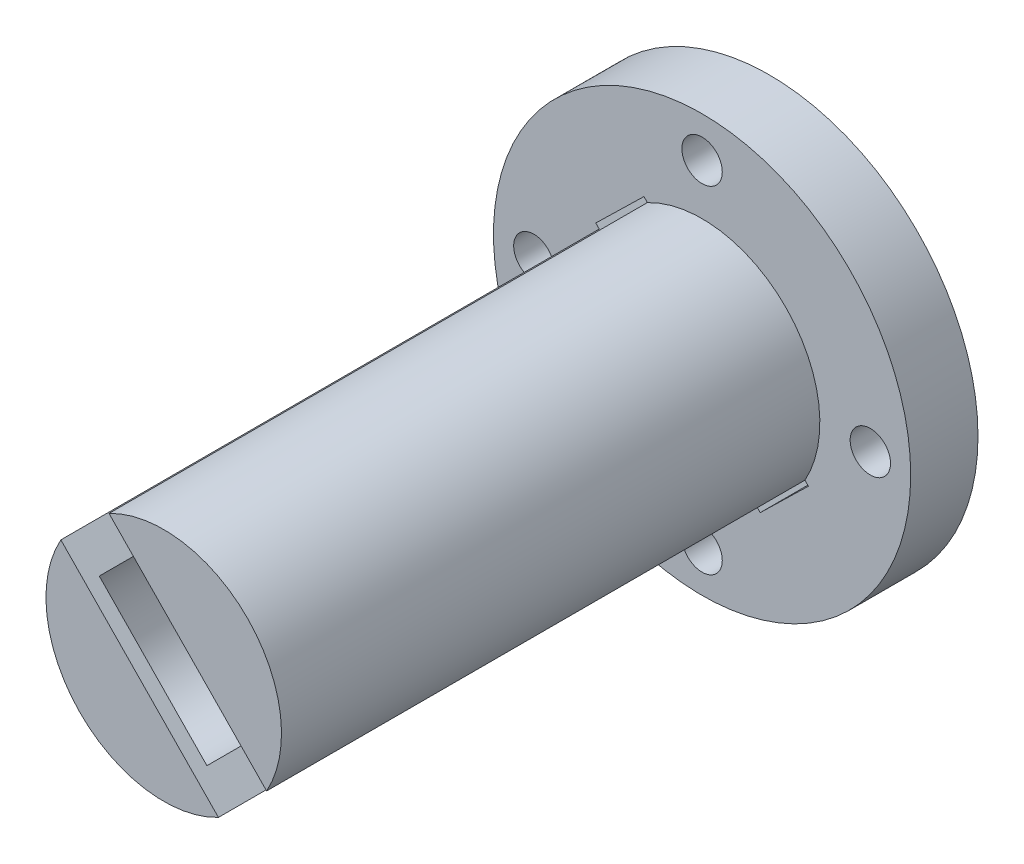
SolidWorks part; units mm, degrees
ref_plane "Спереди" through (0, 0, 0) normal (0, 0, 1) x (1, 0, 0)
ref_plane "Сверху" through (0, 0, 0) normal (0, 1, 0) x (1, 0, 0)
ref_plane "Справа" through (0, 0, 0) normal (1, 0, 0) x (0, 0, -1)
sketch "Эскиз4" plane through (0, 0, 0) normal (0, 0, 1) x (1, 0, 0)
  circle A0 centre (0, 0) radius 12.5
  dimension "D1" = 25
sketch "Эскиз5" plane through (0, 0, 0) normal (0, 0, 1) x (1, 0, 0)
  circle A0 centre (0, 0) radius 31
  dimension "D1" = 62
sketch "Эскиз6" plane through (0, 0, 0) normal (0, 0, 1) x (1, 0, 0)
  circle A0 centre (0, -25) radius 3
  circle A1 centre (-25, 0) radius 3
  circle A2 centre (0, 25) radius 3
  circle A3 centre (25, 0) radius 3
  point P12 (0, 0)
  dimension "D1" = 6
  dimension "D2" = 25
  dimension "D3" = 4
extrude "Бобышка-Вытянуть4" add sketch "Эскиз5" along normal blind 10
extrude "Вырез-Вытянуть5" cut sketch "Эскиз6" along normal blind 10
sketch "Эскиз8" plane through (0, 0, 0) normal (0, 0, 1) x (1, 0, 0)
  circle A0 centre (0, 0) radius 17.5
  dimension "D1" = 35
extrude "Бобышка-Вытянуть5" add sketch "Эскиз8" along normal blind 90
extrude "Вырез-Вытянуть6" cut sketch "Эскиз4" along normal blind 88
sketch "Эскиз11" plane through (0, 0, 0) normal (0, 0, 1) x (1, 0, 0)
  line L7 (-4, 17.5) -> (4, 17.5)
  line L8 (-4, 17.5) -> (-4, -17.5)
  line L9 (-4, -17.5) -> (4, -17.5)
  line L10 (4, 17.5) -> (4, -17.5)
  line L11 (-4, 17.5) -> (4, -17.5) construction
  line L12 (-4, -17.5) -> (4, 17.5) construction
  point P1 (0, 0)
  point P2 (0, 0)
  point P8 (0, 0)
  dimension "D1" = 8
  dimension "D2" = 35
extrude "Вырез-Вытянуть9" [suppressed] cut sketch "Эскиз11" along normal blind 90
sketch "Эскиз12" plane through (0, 0, 0) normal (0, 0, 1) x (1, 0, 0)
  line L0 (0, 0) -> (-65.7464, 65.7464)
  line L1 (8.6402, -16.0187) -> (-15.7987, 9.0361)
  line L2 (0, 0) -> (65.7464, -65.7464)
  line L3 (8.6402, -16.0187) -> (15.7987, -9.0361)
  line L4 (-15.7987, 9.0361) -> (-8.6402, 16.0187)
  line L5 (15.7987, -9.0361) -> (-8.6402, 16.0187)
  line L6 (8.6402, -16.0187) -> (-8.6402, 16.0187) construction
  line L7 (-15.7987, 9.0361) -> (15.7987, -9.0361) construction
  point P8 (0, 0)
  dimension "D1" = 35
  dimension "D2" = 10
  dimension "D3" = 2
ref_axis "Ось1" through (0, 0, 0) along (0.7071, -0.7071, 0)
extrude "Вырез-Вытянуть10" cut sketch "Эскиз12" along normal blind 120 contours L1 L4 L5 L3
